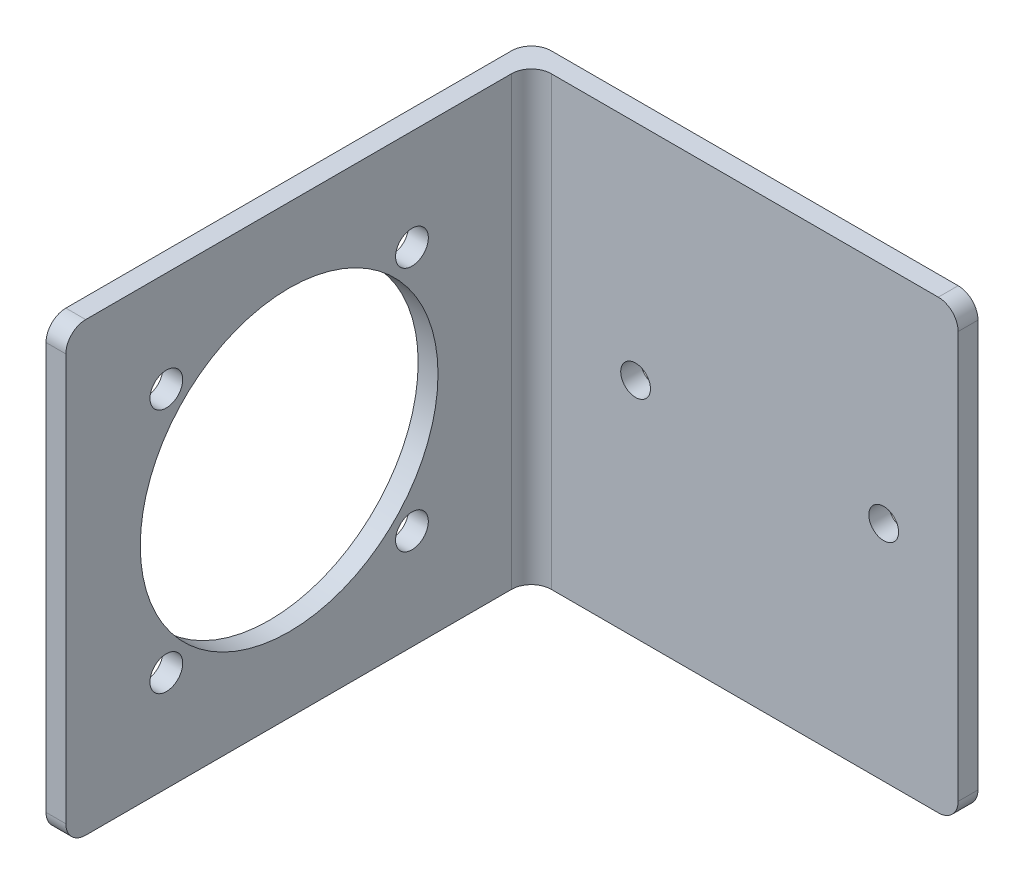
SolidWorks part; units mm, degrees
material "1023 碳钢板 (SS)"
ref_plane "前视基准面" through (0, 0, 0) normal (0, 0, 1) x (1, 0, 0)
ref_plane "上视基准面" through (0, 0, 0) normal (0, 1, 0) x (1, 0, 0)
ref_plane "右视基准面" through (0, 0, 0) normal (1, 0, 0) x (0, 0, -1)
other "Configuration Table"
sketch "草图1" plane through (0, 0, 0) normal (0, 1, 0) x (1, 0, 0)
  line L0 (0, 0) -> (0, 48.91)
  line L1 (0, 48.91) -> (45, 48.91)
  dimension "D1" = 48.91
  dimension "D2" = 45
extrude "拉伸-薄壁1" add sketch "草图1" along normal blind 45 thin thin type one direction wall 2
fillet "圆角1" radius 2 2 edges at (2, 22.5, -46.91) (0, 22.5, -48.91)
sketch "草图2" plane through (0, 0, 0) normal (-1, 0, 0) x (0, 0, 1)
  line L0 (0, 0) -> (-46.91, 0) construction
  line L1 (0, 45) -> (0, 0) construction
  circle A0 centre (-22.5, 22.5) radius 15
  dimension "D1" = 30
  dimension "D2" = 22.5
  dimension "D3" = 22.5
extrude "切除-拉伸1" cut sketch "草图2" against normal blind 10
fillet "圆角2" radius 2 4 edges at (45, 0, -47.91) (45, 45, -47.91) (1, 0, 0) (1, 45, 0)
sketch "草图3" plane through (0, 0, 0) normal (-1, 0, 0) x (0, 0, 1)
  circle A0 centre (-22.5, 22.5) radius 17.5 construction
  circle A1 centre (-11.5674, 36.1649) radius 1.7404
  circle A2 centre (-12.103, 8.4234) radius 2.4153
  dimension "D1" = 35
sketch "草图4" plane through (0, 0, 0) normal (-1, 0, 0) x (0, 0, 1)
  circle A1 centre (-34.8744, 10.1256) radius 1.65
  circle A2 centre (-34.8744, 10.1256) radius 1.65
  circle A3 centre (-10.1256, 10.1256) radius 1.65
  circle A4 centre (-10.1256, 10.1256) radius 1.65
  circle A5 centre (-10.1256, 34.8744) radius 1.65
  circle A6 centre (-10.1256, 34.8744) radius 1.65
  circle A7 centre (-34.8744, 34.8744) radius 1.65
  circle A8 centre (-34.8744, 34.8744) radius 1.65
  dimension "D1" = 0
  dimension "D2" = 0
  dimension "D3" = 0
  dimension "D4" = 0
extrude "切除-拉伸2" cut sketch "草图4" against normal blind 10
sketch "草图5" plane through (0, 0, -46.91) normal (0, 0, 1) x (1, 0, 0)
  line L0 (45, 43) -> (45, 2) construction
  line L1 (4, 45) -> (43, 45) construction
  circle A0 centre (12.5, 22.5) radius 1.5
  circle A1 centre (37.5, 22.5) radius 1.5
  dimension "D2" = 3
  dimension "D3" = 3
  dimension "D1" = 25
  dimension "D4" = 7.5
  dimension "D5" = 22.5
  dimension "D6" = 22.5
extrude "切除-拉伸3" cut sketch "草图5" against normal blind 10
